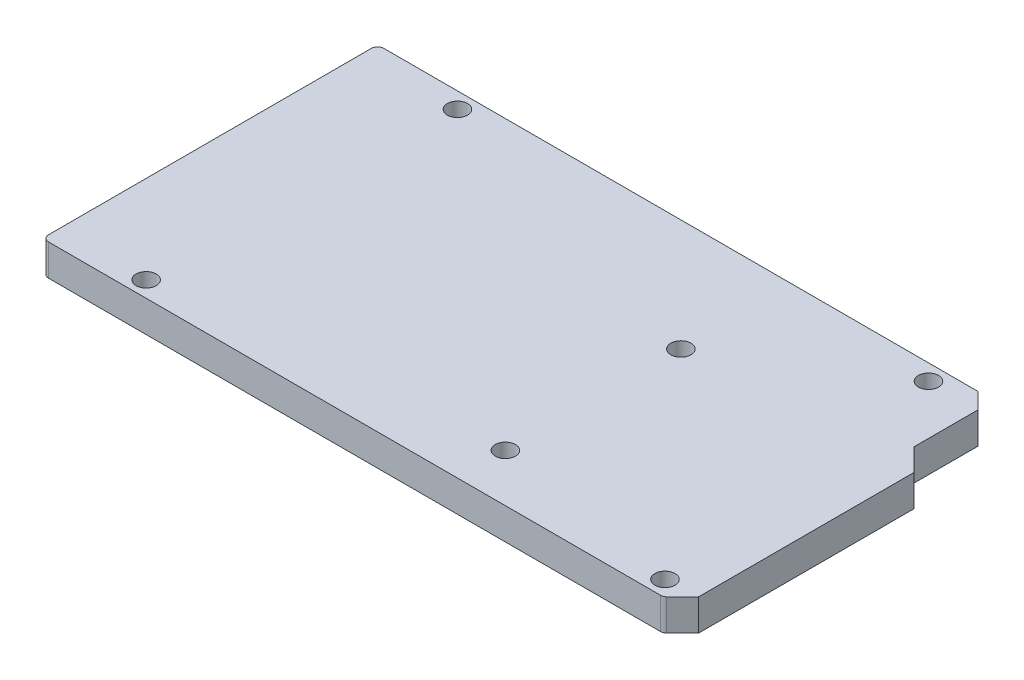
SolidWorks part; units mm, degrees
ref_plane "Front Plane" through (0, 0, 0) normal (0, 0, 1) x (1, 0, 0)
ref_plane "Top Plane" through (0, 0, 0) normal (0, 1, 0) x (1, 0, 0)
ref_plane "Right Plane" through (0, 0, 0) normal (1, 0, 0) x (0, 0, -1)
sketch "Sketch1" plane through (0, 0, 0) normal (0, 1, 0) x (1, 0, 0)
  line L0 (-50.76, -26.65) -> (-50.76, 26.65)
  line L1 (-50.76, -26.65) -> (50.76, -26.65) construction
  line L2 (-50.76, -26.65) -> (-50.76, 26.65) construction
  line L3 (-50.76, 26.65) -> (50.76, 26.65) construction
  line L4 (50.76, -26.65) -> (50.76, 26.65) construction
  line L5 (-50.76, -26.65) -> (50.76, 26.65) construction
  line L6 (-50.76, 26.65) -> (50.76, -26.65) construction
  line L7 (-50.76, 26.65) -> (44.689, 26.65)
  line L8 (44.689, 26.65) -> (47.228, 24.111)
  line L9 (47.228, 24.111) -> (47.228, 13.955)
  line L10 (47.228, 13.955) -> (50.76, 10.423)
  line L11 (50.76, 10.423) -> (50.76, -23.834)
  line L12 (-50.76, -26.65) -> (48.221, -26.65)
  line L13 (50.76, -23.834) -> (48.221, -26.373)
  line L14 (48.221, -26.373) -> (48.221, -26.65)
  point P0 (0, 0)
  point P6 (49.1206, -26.65)
  point P12 (31.6549, 24.6968)
  point P15 (31.621, 22.9556)
  point P16 (38.4389, 13.2239)
  point P17 (47.7232, 23.6158)
  point P18 (48.1924, -26.65)
  point P19 (49.3726, -25.2214)
  point P20 (49.8555, -24.7385)
  point P21 (0, 0)
  point P22 (47.4706, 23.8684)
  dimension "D1" = 53.3
  dimension "D2" = 101.52
  dimension "D3" = 45
  dimension "D4" = 45
  dimension "D5" = 45
  dimension "D6" = 95.449
  dimension "D7" = 34.257
  dimension "D8" = 2.539
  dimension "D9" = 10.156
  dimension "D10" = 2.539
extrude "Boss-Extrude1" add sketch "Sketch1" along normal blind 5
sketch "Sketch2" plane through (0, 0, 0) normal (0, 1, 0) x (1, 0, 0)
  line L0 (-50.76, 26.65) -> (-50.76, -26.65) construction
  line L1 (44.689, 26.65) -> (-50.76, 26.65) construction
  line L2 (-50.76, -26.65) -> (48.221, -26.65) construction
  circle A0 centre (-35.525, 24.111) radius 1.608
  circle A1 centre (-36.795, -24.111) radius 1.608
  circle A2 centre (15.235, 8.876) radius 1.608
  circle A3 centre (15.235, -19.033) radius 1.608
  circle A4 centre (39.357, 24.111) radius 1.608
  circle A5 centre (45.684, -24.111) radius 1.608
  point P18 (7.2575, -11.6417)
  point P19 (37.8965, 22.9235)
  dimension "D1" = 3.216
  dimension "D2" = 15.235
  dimension "D4" = 13.965
  dimension "D5" = 2.539
  dimension "D6" = 65.995
  dimension "D7" = 17.774
  dimension "D9" = 90.117
  dimension "D10" = 7.617
  dimension "D11" = 2.539
  dimension "D12" = 65.995
  dimension "D13" = 96.444
  dimension "D3" = 2.539
  dimension "D8" = 2.539
extrude "Cut-Extrude1" cut sketch "Sketch2" along normal through all
fillet "Fillet1" radius 0.994 3 edges at (48.221, 2.5, 26.65) (-50.76, 2.5, 26.65) (-50.76, 2.5, -26.65)
